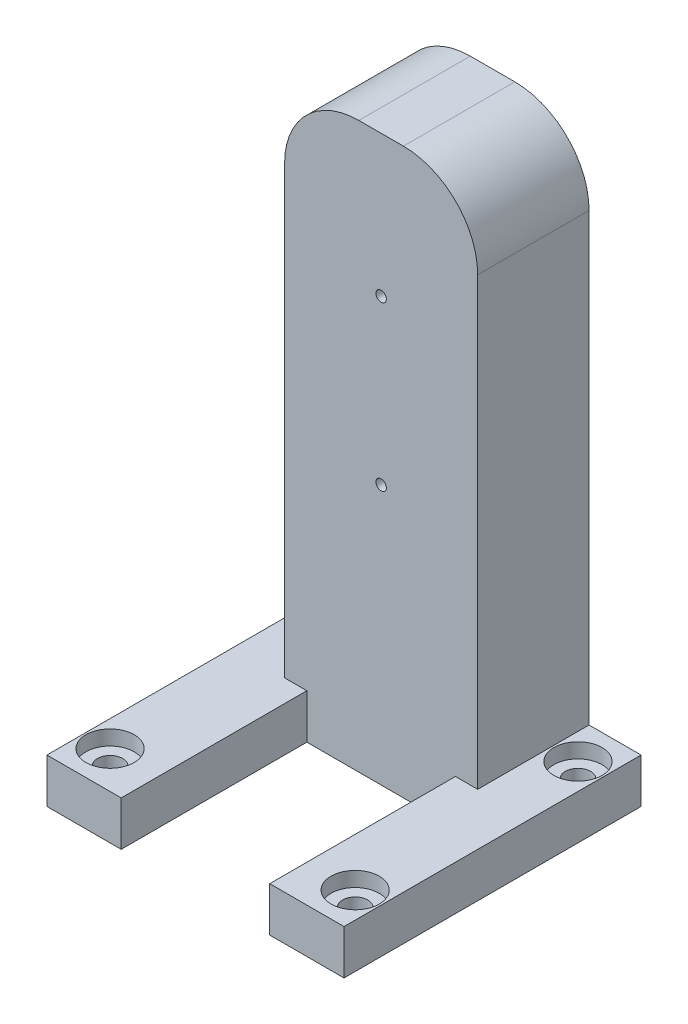
SolidWorks part; units mm, degrees
ref_plane "Plan de face" through (0, 0, 0) normal (0, 0, 1) x (1, 0, 0)
ref_plane "Plan de dessus" through (0, 0, 0) normal (0, 1, 0) x (1, 0, 0)
ref_plane "Plan de droite" through (0, 0, 0) normal (1, 0, 0) x (0, 0, -1)
sketch "Esquisse1" plane through (0, 0, 0) normal (0, 0, 1) x (1, 0, 0)
  line L0 (0, 0) -> (-20, 0)
  line L1 (-20, 0) -> (20, 0) construction
  line L2 (-20, 0) -> (-20, 76) construction
  line L3 (-20, 76) -> (20, 76) construction
  line L4 (20, 0) -> (20, 76) construction
  line L5 (-20, 0) -> (-20, 6)
  line L6 (-20, 6) -> (-13, 6)
  line L7 (-13, 6) -> (-13, 76)
  line L8 (-13, 76) -> (13, 76)
  line L9 (13, 76) -> (13, 6)
  line L10 (13, 6) -> (20, 6)
  line L11 (20, 6) -> (20, 0)
  line L12 (20, 0) -> (0, 0)
  point P4 (0, 0)
  dimension "D1" = 26
  dimension "D2" = 70
  dimension "D3" = 7
  dimension "D4" = 7
  dimension "D5" = 6
  dimension "D6" = 6
extrude "Boss.-Extru.1" add sketch "Esquisse1" along normal blind 15
sketch "Esquisse2" plane through (0, 0, 0) normal (0, -1, 0) x (1, 0, 0)
  line L1 (-20, 15) -> (20, 15) construction
  line L2 (-20, 15) -> (-20, 40) construction
  line L3 (-20, 40) -> (20, 40) construction
  line L4 (20, 15) -> (20, 40) construction
  line L5 (-20, 40) -> (-10, 40)
  line L6 (-20, 40) -> (-20, 15)
  line L7 (-20, 15) -> (-10, 15)
  line L8 (-10, 40) -> (-10, 15)
  line L9 (20, 40) -> (10, 40)
  line L10 (20, 40) -> (20, 15)
  line L11 (20, 15) -> (10, 15)
  line L12 (10, 40) -> (10, 15)
  dimension "D1" = 25
  dimension "D2" = 40
  dimension "D3" = 10
  dimension "D4" = 10
extrude "Boss.-Extru.2" add sketch "Esquisse2" against normal blind 6
sketch "Esquisse3" plane through (0, 0, 15) normal (0, 0, 1) x (1, 0, 0)
  line L0 (0, 76) -> (0, 0) construction
  line L1 (13, 76) -> (-13, 76) construction
  line L2 (-10, 0) -> (10, 0) construction
  circle A0 centre (0, 57) radius 1
  circle A1 centre (0, 35) radius 1
  dimension "D1" = 2
  dimension "D2" = 2
  dimension "D3" = 22
  dimension "D4" = 35
sketch "Esquisse4" plane through (0, 6, 0) normal (0, 1, 0) x (1, 0, 0)
  line L0 (-16.5, 0) -> (-16.5, -40) construction
  line L1 (-13, 0) -> (-20, 0) construction
  line L2 (16.5, 0) -> (16.5, -40) construction
  line L3 (20, 0) -> (13, 0) construction
  line L4 (-10, -40) -> (-20, -40) construction
  line L5 (20, -40) -> (10, -40) construction
  circle A0 centre (-16.5, -5) radius 1
  circle A1 centre (16.5, -5) radius 1
  circle A2 centre (16.5, -35) radius 1
  circle A3 centre (-16.5, -35) radius 1
  dimension "D1" = 2
  dimension "D2" = 2
  dimension "D3" = 2
  dimension "D4" = 2
  dimension "D5" = 5
  dimension "D6" = 5
  dimension "D7" = 5
  dimension "D8" = 5
hole_wizard "Dégagement M1.21" positions "Esquisse5" profile "Esquisse7" hole size "M1.2" standard "ISO" end condition through all
sketch "Esquisse5" plane through (0, 0, 15) normal (0, 0, 1) x (1, 0, 0)
  point P0 (0, 57)
  point P3 (0, 35)
sketch "Esquisse7" plane through (0, 57, 15) normal (1, 0, 0) x (0, -1, 0)
  line L0 (0, 0) -> (0, 15)
  line L1 (0, 15) -> (0.7, 15)
  line L2 (0.7, 15) -> (0.7, 0)
  line L5 (0.7, 0) -> (0, 0)
  line L11 (0, -6.35) -> (0, 107.95) construction
  dimension "Diamètre du perçage jusqu'au prochain" = 1.4
  dimension "Profondeur du perçage jusqu'au prochain" = 15
hole_wizard "Chambrage pour tête cylindrique fendue M31" positions "Esquisse8" profile "Esquisse9" counterbore size "M3" standard "ISO" end condition through all
sketch "Esquisse8" plane through (0, 6, 0) normal (0, 1, 0) x (1, 0, 0)
  point P0 (-16.5, -5)
  point P3 (16.5, -5)
  point P6 (16.5, -35)
  point P9 (-16.5, -35)
sketch "Esquisse9" plane through (-16.5, 6, 5) normal (1, 0, 0) x (0, 0, 1)
  line L0 (0, 0) -> (0, 6)
  line L1 (0, 6) -> (1.7, 6)
  line L3 (1.7, 6) -> (1.7, 2)
  line L4 (1.7, 2) -> (3.25, 2)
  line L5 (3.25, 2) -> (3.25, 0)
  line L7 (3.25, 0) -> (0, 0)
  line L11 (0, -6.35) -> (0, 107.95) construction
  dimension "Diamètre du perçage jusqu'au prochain" = 3.4
  dimension "Profondeur du perçage jusqu'au prochain" = 6
  dimension "Diamètre du chambrage" = 6.5
  dimension "Profondeur du chambrage" = 2
fillet "Congé1" radius 10 2 edges at (13, 76, 7.5) (-13, 76, 7.5)
equation "\"hauteur\"= 35'hauteur vis du bas"
equation "\"D4@Esquisse3\"=\"hauteur\""
